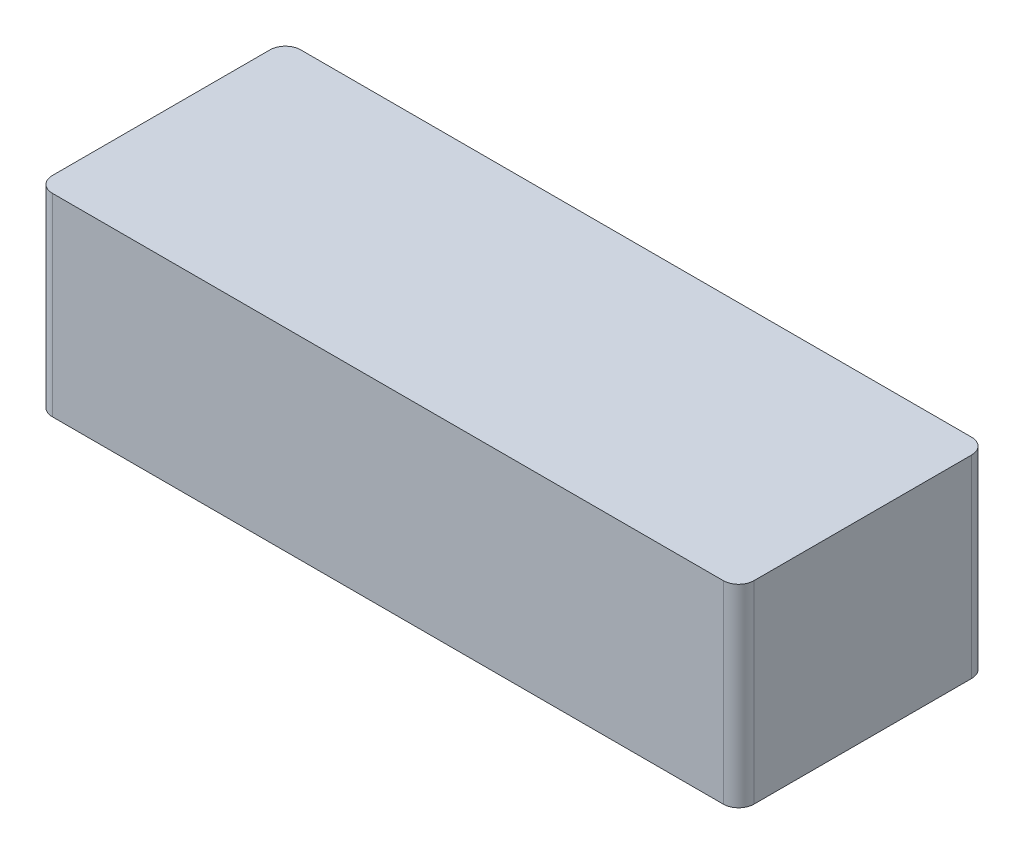
SolidWorks part; units mm, degrees
material "Nylon 6/10"
ref_plane "Front Plane" through (0, 0, 0) normal (0, 0, 1) x (1, 0, 0)
ref_plane "Top Plane" through (0, 0, 0) normal (0, 1, 0) x (1, 0, 0)
ref_plane "Right Plane" through (0, 0, 0) normal (1, 0, 0) x (0, 0, -1)
sketch "Sketch1" plane through (0, 0, 0) normal (0, 1, 0) x (1, 0, 0)
  line L0 (-68.5, -21.25) -> (-68.5, 21.25)
  line L1 (-65.5, -23.25) -> (65.5, -23.25) construction
  line L2 (-67.5, -21.25) -> (-67.5, 21.25) construction
  line L3 (-65.5, 23.25) -> (65.5, 23.25) construction
  line L4 (67.5, -21.25) -> (67.5, 21.25) construction
  line L5 (-67.5, -23.25) -> (67.5, 23.25) construction
  line L6 (-67.5, 23.25) -> (67.5, -23.25) construction
  line L7 (-65.5, 24.25) -> (65.5, 24.25)
  line L8 (68.5, -21.25) -> (68.5, 21.25)
  line L9 (-65.5, -24.25) -> (65.5, -24.25)
  arc A0 (65.5, 23.25) -> (67.5, 21.25) centre (65.5, 21.25) cw construction
  arc A1 (65.5, -23.25) -> (67.5, -21.25) centre (65.5, -21.25) ccw construction
  arc A2 (-65.5, -23.25) -> (-67.5, -21.25) centre (-65.5, -21.25) cw construction
  arc A3 (-67.5, 21.25) -> (-65.5, 23.25) centre (-65.5, 21.25) cw construction
  arc A4 (-68.5, 21.25) -> (-65.5, 24.25) centre (-65.5, 21.25) cw
  arc A5 (65.5, 24.25) -> (68.5, 21.25) centre (65.5, 21.25) cw
  arc A6 (65.5, -24.25) -> (68.5, -21.25) centre (65.5, -21.25) ccw
  arc A7 (-65.5, -24.25) -> (-68.5, -21.25) centre (-65.5, -21.25) cw
  point P0 (0, 0)
  dimension "D3" = 2
  dimension "D1" = 135
  dimension "D2" = 46.5
  dimension "D4" = 1
extrude "Boss-Extrude1" add sketch "Sketch1" along normal blind 31.5
shell "Shell1" thickness 1 removed face at (0, 0, 0)
sketch "Sketch2" plane through (0, 0, 0) normal (0, 1, 0) x (1, 0, 0)
  line L0 (-68.5, 21.25) -> (-68.5, 17)
  line L1 (-63.5, 19.25) -> (63.5, 19.25) construction
  line L2 (-63.5, 19.25) -> (-63.5, -19.25) construction
  line L3 (-63.5, -19.25) -> (63.5, -19.25) construction
  line L4 (63.5, 19.25) -> (63.5, -19.25) construction
  line L5 (-63.5, 19.25) -> (63.5, -19.25) construction
  line L6 (-63.5, -19.25) -> (63.5, 19.25) construction
  line L7 (-65.5, 23.25) -> (-61.25, 23.25) construction
  line L8 (-67.5, 21.25) -> (-67.5, 17) construction
  line L9 (-65.5, -23.25) -> (65.5, -23.25) construction
  line L10 (67.5, 21.25) -> (67.5, 17) construction
  line L11 (-67.5, 23.25) -> (67.5, -23.25) construction
  line L12 (-67.5, -23.25) -> (67.5, 23.25) construction
  line L13 (-65.5, -24.25) -> (-61.25, -24.25)
  line L14 (68.5, 21.25) -> (68.5, 17)
  line L15 (-65.5, 24.25) -> (-61.25, 24.25)
  line L16 (-63.5, -17) -> (-68.5, -17)
  line L17 (-61.25, -19.25) -> (-61.25, -24.25)
  line L18 (-65.5, -24.25) -> (65.5, -24.25) construction
  line L19 (-63.5, 17) -> (-68.5, 17)
  line L20 (-61.25, 19.25) -> (-61.25, 24.25)
  line L21 (61.25, 19.25) -> (61.25, 24.25)
  line L22 (63.5, 17) -> (68.5, 17)
  line L23 (61.25, -19.25) -> (61.25, -24.25)
  line L24 (-65.5, -24.25) -> (65.5, -24.25) construction
  line L25 (63.5, -17) -> (68.5, -17)
  line L26 (65.5, -24.25) -> (61.25, -24.25)
  line L27 (68.5, -17) -> (68.5, -21.25)
  line L28 (68.5, 21.25) -> (68.5, -21.25) construction
  line L29 (-68.5, -17) -> (-68.5, -21.25)
  line L30 (-68.5, 21.25) -> (-68.5, -21.25) construction
  line L31 (-67.5, -17) -> (-67.5, -21.25) construction
  line L32 (-67.5, 21.25) -> (-67.5, -21.25) construction
  line L33 (61.25, 24.25) -> (65.5, 24.25)
  line L34 (-65.5, 24.25) -> (65.5, 24.25) construction
  line L35 (61.25, 23.25) -> (65.5, 23.25) construction
  line L36 (-65.5, 23.25) -> (65.5, 23.25) construction
  line L37 (67.5, -17) -> (67.5, -21.25) construction
  line L38 (67.5, 21.25) -> (67.5, -21.25) construction
  arc A0 (-61.25, -19.25) -> (-63.5, -17) centre (-63.5, -19.25) ccw
  arc A1 (63.5, -17) -> (61.25, -19.25) centre (63.5, -19.25) ccw
  arc A2 (61.25, 19.25) -> (63.5, 17) centre (63.5, 19.25) ccw
  arc A3 (-63.5, 17) -> (-61.25, 19.25) centre (-63.5, 19.25) ccw
  arc A4 (65.5, -23.25) -> (67.5, -21.25) centre (65.5, -21.25) ccw construction
  arc A5 (65.5, 23.25) -> (67.5, 21.25) centre (65.5, 21.25) cw construction
  arc A6 (-65.5, 23.25) -> (-67.5, 21.25) centre (-65.5, 21.25) ccw construction
  arc A7 (-67.5, -21.25) -> (-65.5, -23.25) centre (-65.5, -21.25) ccw construction
  arc A8 (-68.5, -21.25) -> (-65.5, -24.25) centre (-65.5, -21.25) ccw
  arc A9 (65.5, -24.25) -> (68.5, -21.25) centre (65.5, -21.25) ccw
  arc A10 (65.5, 24.25) -> (68.5, 21.25) centre (65.5, 21.25) cw
  arc A11 (-65.5, 24.25) -> (-68.5, 21.25) centre (-65.5, 21.25) ccw
  point P0 (0, 0)
  point P9 (0, 0)
  dimension "D3" = 4.5
  dimension "D6" = 2
  dimension "D1" = 127
  dimension "D2" = 38.5
  dimension "D4" = 135
  dimension "D5" = 46.5
  dimension "D7" = 1
extrude "Boss-Extrude2" add sketch "Sketch2" along normal up to surface (30.5 mm away) up to face at (0, 30.5, 0)
sketch "Sketch4" plane through (0, 0, 0) normal (0, 1, 0) x (1, 0, 0)
  line L0 (-68.5, -21.25) -> (-68.5, 21.25)
  line L1 (-65.5, -23.25) -> (65.5, -23.25)
  line L2 (-67.5, -21.25) -> (-67.5, 21.25)
  line L3 (-65.5, 23.25) -> (65.5, 23.25)
  line L4 (67.5, -21.25) -> (67.5, 21.25)
  line L5 (-67.5, -23.25) -> (67.5, 23.25) construction
  line L6 (-67.5, 23.25) -> (67.5, -23.25) construction
  line L7 (-65.5, 24.25) -> (65.5, 24.25)
  line L8 (68.5, -21.25) -> (68.5, 21.25)
  line L9 (-65.5, -24.25) -> (65.5, -24.25)
  arc A0 (65.5, 23.25) -> (67.5, 21.25) centre (65.5, 21.25) cw
  arc A1 (65.5, -23.25) -> (67.5, -21.25) centre (65.5, -21.25) ccw
  arc A2 (-65.5, -23.25) -> (-67.5, -21.25) centre (-65.5, -21.25) cw
  arc A3 (-67.5, 21.25) -> (-65.5, 23.25) centre (-65.5, 21.25) cw
  arc A4 (-68.5, 21.25) -> (-65.5, 24.25) centre (-65.5, 21.25) cw
  arc A5 (65.5, 24.25) -> (68.5, 21.25) centre (65.5, 21.25) cw
  arc A6 (65.5, -24.25) -> (68.5, -21.25) centre (65.5, -21.25) ccw
  arc A7 (-65.5, -24.25) -> (-68.5, -21.25) centre (-65.5, -21.25) cw
  point P0 (0, 0)
  dimension "D3" = 2
  dimension "D1" = 135
  dimension "D2" = 46.5
  dimension "D4" = 1
extrude "Boss-Extrude4" add sketch "Sketch4" against normal blind 6.3
sketch "Sketch5" plane through (0, 0, 0) normal (0, -1, 0) x (1, 0, 0)
  line L1 (-63.5, -19.25) -> (63.5, -19.25) construction
  line L2 (-63.5, -19.25) -> (-63.5, 19.25) construction
  line L3 (-63.5, 19.25) -> (63.5, 19.25) construction
  line L4 (63.5, -19.25) -> (63.5, 19.25) construction
  line L5 (-63.5, -19.25) -> (63.5, 19.25) construction
  line L6 (-63.5, 19.25) -> (63.5, -19.25) construction
  circle A0 centre (-63.5, 19.25) radius 1.5
  circle A1 centre (-63.5, -19.25) radius 1.5
  circle A2 centre (63.5, 19.25) radius 1.5
  circle A3 centre (63.5, -19.25) radius 1.5
  point P0 (0, 0)
  dimension "D3" = 3
  dimension "D1" = 127
  dimension "D2" = 38.5
extrude "Cut-Extrude2" cut sketch "Sketch5" against normal blind 5
